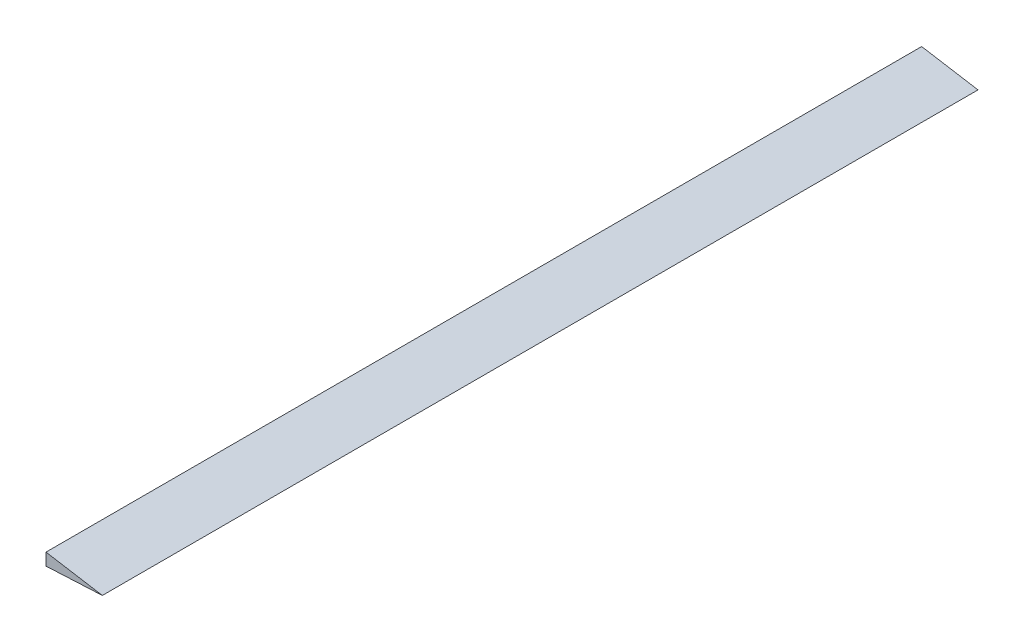
SolidWorks part; units mm, degrees
material "Balsa"
ref_plane "Front Plane" through (0, 0, 0) normal (0, 0, 1) x (1, 0, 0)
ref_plane "Top Plane" through (0, 0, 0) normal (0, 1, 0) x (1, 0, 0)
ref_plane "Right Plane" through (0, 0, 0) normal (1, 0, 0) x (0, 0, -1)
sketch "Sketch1" plane through (0, 0, 0) normal (0, 0, 1) x (1, 0, 0)
  line L0 (306.8496, -2.5161) -> (306.8496, 8.4499) construction
  line L1 (306.8496, -2.5161) -> (306.8496, 8.4499)
  line L2 (306.8496, 8.4499) -> (357.6496, 0)
  line L3 (306.8496, -2.5161) -> (357.6496, 0)
  spline S0 degree 3 poles (354.9573, 0.0431) (358.3317, -0.0432) (354.9981, 0.2938) (352.3707, 0.8024) (346.1763, 1.8676) (338.7813, 3.2655) (329.3081, 4.8919) (318.2482, 6.6648) (305.5952, 8.6507) (291.564, 10.8193) (276.34, 13.1505) (260.1392, 15.5903) (243.1815, 18.0913) (225.699, 20.6027) (207.9209, 23.0318) (190.087, 25.3152) (172.4086, 27.3328) (155.0467, 28.9096) (138.1258, 29.947) (121.7437, 30.3922) (105.9899, 30.2108) (90.9433, 29.4155) (76.6903, 28.0308) (63.3272, 26.1868) (50.9728, 23.9485) (39.7523, 21.3791) (29.7714, 18.545) (21.1318, 15.5018) (13.8914, 12.3237) (8.1391, 9.1075) (3.8158, 5.9031) (1.1802, 2.9693) (-0.4877, -0.018) (1.2572, -2.9285) (4.805, -4.6528) (9.8754, -6.6365) (16.78, -8.2511) (25.3535, -9.7017) (35.5828, -10.8813) (47.3622, -11.8027) (60.5842, -12.4624) (75.1117, -12.8607) (90.7897, -13.0132) (107.4435, -12.9137) (124.9052, -12.5651) (143.0256, -11.8868) (161.6617, -10.9405) (180.6424, -9.8572) (199.7442, -8.7119) (218.721, -7.5525) (237.3263, -6.4253) (255.3201, -5.3536) (272.4652, -4.367) (288.5372, -3.4753) (303.3148, -2.6922) (316.6121, -2.0207) (328.2104, -1.4385) (338.1246, -0.9102) (345.8395, -0.4061) (352.2525, -0.129) (354.9573, 0.0431) (358.3317, -0.0432) (354.9981, 0.2938) knots -0.015092 -0.006889 -0.001754 0 0.001748 0.006827 0.01488 0.025572 0.038694 0.054171 0.071834 0.091435 0.112685 0.135293 0.158944 0.183315 0.20807 0.232879 0.257399 0.281384 0.304706 0.327241 0.348897 0.369607 0.389308 0.407886 0.425177 0.441027 0.4553 0.467904 0.478752 0.487814 0.49509 0.500617 0.504451 0.507804 0.513091 0.520546 0.530249 0.542214 0.556382 0.572656 0.590895 0.610925 0.632536 0.655496 0.679547 0.704499 0.730211 0.756436 0.782837 0.809062 0.834776 0.859641 0.883338 0.905541 0.925965 0.944326 0.960366 0.973929 0.984908 0.993111 0.998246 1 1.001748 1.006827 1.01488 only from (357.6496, 0) to (357.6496, 0) construction
  spline S1 degree 3 poles (354.9573, 0.0431) (358.3317, -0.0432) (354.9981, 0.2938) (352.3707, 0.8024) (346.1763, 1.8676) (338.7813, 3.2655) (329.3081, 4.8919) (318.2482, 6.6648) (305.5952, 8.6507) (291.564, 10.8193) (276.34, 13.1505) (260.1392, 15.5903) (243.1815, 18.0913) (225.699, 20.6027) (207.9209, 23.0318) (190.087, 25.3152) (172.4086, 27.3328) (155.0467, 28.9096) (138.1258, 29.947) (121.7437, 30.3922) (105.9899, 30.2108) (90.9433, 29.4155) (76.6903, 28.0308) (63.3272, 26.1868) (50.9728, 23.9485) (39.7523, 21.3791) (29.7714, 18.545) (21.1318, 15.5018) (13.8914, 12.3237) (8.1391, 9.1075) (3.8158, 5.9031) (1.1802, 2.9693) (-0.4877, -0.018) (1.2572, -2.9285) (4.805, -4.6528) (9.8754, -6.6365) (16.78, -8.2511) (25.3535, -9.7017) (35.5828, -10.8813) (47.3622, -11.8027) (60.5842, -12.4624) (75.1117, -12.8607) (90.7897, -13.0132) (107.4435, -12.9137) (124.9052, -12.5651) (143.0256, -11.8868) (161.6617, -10.9405) (180.6424, -9.8572) (199.7442, -8.7119) (218.721, -7.5525) (237.3263, -6.4253) (255.3201, -5.3536) (272.4652, -4.367) (288.5372, -3.4753) (303.3148, -2.6922) (316.6121, -2.0207) (328.2104, -1.4385) (338.1246, -0.9102) (345.8395, -0.4061) (352.2525, -0.129) (354.9573, 0.0431) (358.3317, -0.0432) (354.9981, 0.2938) knots -0.015092 -0.006889 -0.001754 0 0.001748 0.006827 0.01488 0.025572 0.038694 0.054171 0.071834 0.091435 0.112685 0.135293 0.158944 0.183315 0.20807 0.232879 0.257399 0.281384 0.304706 0.327241 0.348897 0.369607 0.389308 0.407886 0.425177 0.441027 0.4553 0.467904 0.478752 0.487814 0.49509 0.500617 0.504451 0.507804 0.513091 0.520546 0.530249 0.542214 0.556382 0.572656 0.590895 0.610925 0.632536 0.655496 0.679547 0.704499 0.730211 0.756436 0.782837 0.809062 0.834776 0.859641 0.883338 0.905541 0.925965 0.944326 0.960366 0.973929 0.984908 0.993111 0.998246 1 1.001748 1.006827 1.01488 only from (357.6496, 0) to (357.6496, 0)
sketch "Sketch2" plane through (0, 0, -761.9997) normal (0, 0, -1) x (-1, 0, 0)
  line L0 (-306.8496, -2.5161) -> (-306.8496, 8.4499) construction
  line L1 (-306.8496, -2.5161) -> (-357.6496, 0) construction
  line L2 (-306.8496, 8.4499) -> (-357.6496, 0) construction
  line L3 (-306.8496, -2.5161) -> (-306.8496, 8.4499)
  line L4 (-306.8496, -2.5161) -> (-357.6496, 0)
  line L5 (-306.8496, 8.4499) -> (-357.6496, 0)
extrude "Boss-Extrude2" add sketch "Sketch2" against normal blind 789.432
